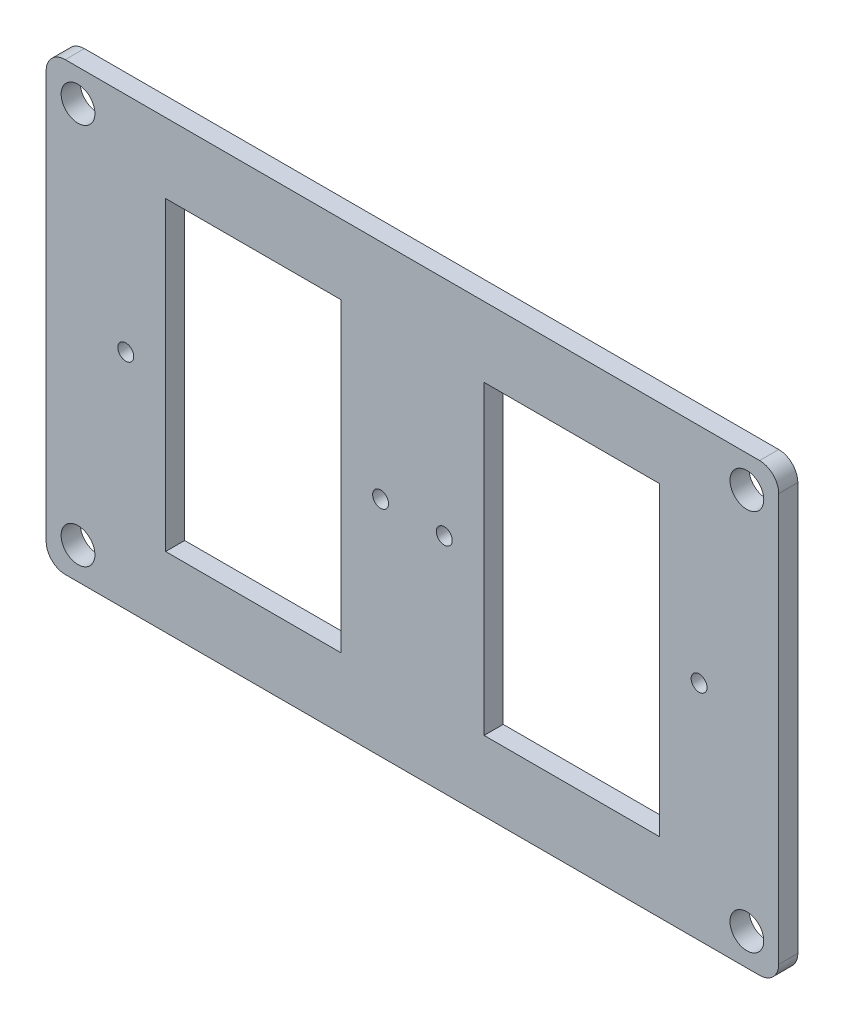
SolidWorks part; units mm, degrees
material "6061-T6 (SS)"
ref_plane "Front Plane" through (0, 0, 0) normal (0, 0, 1) x (1, 0, 0)
ref_plane "Top Plane" through (0, 0, 0) normal (0, 1, 0) x (1, 0, 0)
ref_plane "Right Plane" through (0, 0, 0) normal (1, 0, 0) x (0, 0, -1)
sketch "Sketch1" plane through (0, 0, 0) normal (0, 0, 1) x (1, 0, 0)
  line L0 (-25, 0) -> (0, 0) construction
  line L1 (-11.25, -24) -> (-38.75, -24)
  line L2 (-11.25, -24) -> (-11.25, 24)
  line L3 (-11.25, 24) -> (-38.75, 24)
  line L4 (-38.75, -24) -> (-38.75, 24)
  line L5 (-11.25, -24) -> (-38.75, 24) construction
  line L6 (-11.25, 24) -> (-38.75, -24) construction
  line L11 (11.25, 24) -> (38.75, 24)
  line L12 (57.5, -35) -> (-57.5, -35)
  line L13 (-5, 0) -> (-45, 0) construction
  line L14 (0, -1000) -> (0, 49000) construction
  line L15 (57.5, -35) -> (57.5, 35)
  line L16 (57.5, 35) -> (-57.5, 35)
  line L17 (-57.5, -35) -> (-57.5, 35)
  line L18 (57.5, -35) -> (-57.5, 35) construction
  line L19 (57.5, 35) -> (-57.5, -35) construction
  line L20 (38.75, -24) -> (38.75, 24)
  line L21 (11.25, -24) -> (38.75, -24)
  line L22 (11.25, -24) -> (11.25, 24)
  point P0 (-25, 0)
  point P18 (-25, 0)
  dimension "D1" = 27.5
  dimension "D2" = 48
  dimension "D3" = 40
  dimension "D4" = 25
  dimension "D5" = 115
  dimension "D6" = 70
extrude "Boss-Extrude1" add sketch "Sketch1" along normal blind 3
hole_wizard "Tap Drill for M3x0.5 Tap1" positions "Sketch2" profile "Sketch3" hole size "M3x0.5" standard "ANSI Metric" end condition up to next
sketch "Sketch2" plane through (0, 0, 3) normal (0, 0, 1) x (1, 0, 0)
  line L1 (0, -1.65) -> (0, 1.65) construction
  point P0 (-45, 0)
  point P3 (-5, 0)
  point P12 (45, 0)
  point P13 (5, 0)
sketch "Sketch3" plane through (-45, 0, 3) normal (1, 0, 0) x (0, -1, 0)
  line L0 (0, 0) -> (0, 3)
  line L1 (0, 3) -> (1.25, 3)
  line L2 (1.25, 3) -> (1.25, 0)
  line L5 (1.25, 0) -> (0, 0)
  line L11 (0, -6.35) -> (0, 107.95) construction
  dimension "Thru Hole Dia." = 2.5
  dimension "Thru Hole Depth" = 3
hole_wizard "M5 Clearance Hole1" positions "Sketch4" profile "Sketch5" hole size "M5" standard "ANSI Metric" end condition up to next
sketch "Sketch4" plane through (0, 0, 3) normal (0, 0, 1) x (1, 0, 0)
  line L12 (-52.5, 30) -> (-52.5, -30)
  line L13 (-52.5, -30) -> (52.5, -30)
  line L14 (52.5, -30) -> (52.5, 30)
  line L15 (52.5, 30) -> (-52.5, 30)
  line L16 (-52.5, 30) -> (-52.5, -30)
  line L17 (-52.5, -30) -> (52.5, -30)
  line L18 (52.5, -30) -> (52.5, 30)
  line L19 (52.5, 30) -> (-52.5, 30)
  point P25 (-52.5, 30)
  point P26 (-52.5, -30)
  point P27 (52.5, -30)
  point P28 (52.5, 30)
  dimension "D1" = 5
sketch "Sketch5" plane through (-52.5, 30, 3) normal (1, 0, 0) x (0, -1, 0)
  line L0 (0, 0) -> (0, 3)
  line L1 (0, 3) -> (2.65, 3)
  line L2 (2.65, 3) -> (2.65, 0)
  line L5 (2.65, 0) -> (0, 0)
  line L11 (0, -6.35) -> (0, 107.95) construction
  dimension "Thru Hole Dia." = 5.3
  dimension "Thru Hole Depth" = 3
fillet "Fillet1" radius 3 4 edges at (57.5, 35, 1.5) (57.5, -35, 1.5) (-57.5, -35, 1.5) (-57.5, 35, 1.5)
